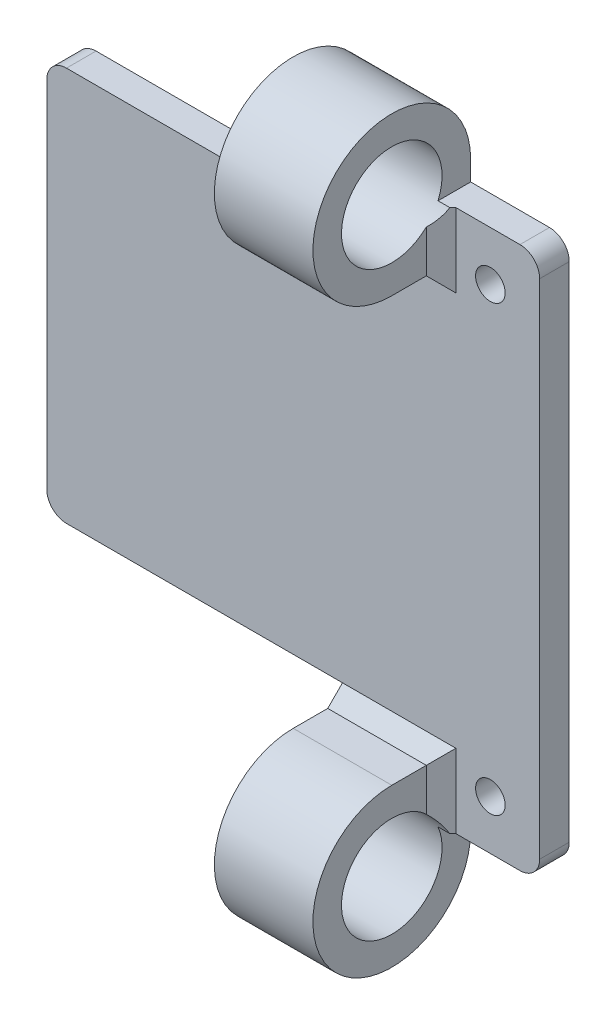
SolidWorks part; units mm, degrees
ref_plane "Front Plane" through (0, 0, 0) normal (0, 0, 1) x (1, 0, 0)
ref_plane "Top Plane" through (0, 0, 0) normal (0, 1, 0) x (1, 0, 0)
ref_plane "Right Plane" through (0, 0, 0) normal (1, 0, 0) x (0, 0, -1)
sketch "Sketch1" plane through (0, 0, 0) normal (0, 0, 1) x (1, 0, 0)
  line L0 (0, 0) -> (25, 0) construction
  line L1 (10, -27.5) -> (25, -27.5)
  line L2 (-25, -20) -> (-25, 20)
  line L3 (-5, 27.5) -> (25, 27.5)
  line L4 (25, -27.5) -> (25, 27.5)
  line L5 (25, 25.5) -> (25, -25.5) construction
  line L7 (20, 22.5) -> (20, -22.5) construction
  line L8 (-5, 27.5) -> (-5, 20)
  line L9 (-5, 20) -> (-25, 20)
  line L10 (-25, -20) -> (10, -20)
  line L11 (10, -20) -> (10, -27.5)
  line L12 (0, 0) -> (-25, 0) construction
  circle A0 centre (0, 22.5) radius 1.5
  circle A1 centre (20, 22.5) radius 1.5
  circle A2 centre (20, -22.5) radius 1.5
  point P0 (0, 0)
  point P14 (20, 0)
  point P21 (-25, 0)
  dimension "D3" = 3
  dimension "D1" = 50
  dimension "D2" = 55
  dimension "D4" = 30
  dimension "D5" = 20
  dimension "D6" = 5
  dimension "D7" = 45
  dimension "D8" = 40
  dimension "D9" = 15
extrude "Boss-Extrude1" add sketch "Sketch1" along normal blind 3
fillet "Fillet1" radius 2 4 edges at (25, 27.5, 1.5) (25, -27.5, 1.5) (-25, -20, 1.5) (-25, 20, 1.5)
sketch "Sketch2" plane through (0, 0, 0) normal (1, 0, 0) x (0, 0, -1)
  line L0 (0, 0) -> (-17.7596, 0) construction
  line L1 (-3, -25.5) -> (-3, 25.5) construction
  line L2 (-8, 21.5) -> (-3, 21.5)
  line L3 (0, -25.5) -> (0, 25.5) construction
  line L10 (0, 11.5) -> (-3, 11.5)
  line L11 (-3, 11.5) -> (-3, 21.5)
  line L12 (0, 11.5) -> (0, 29.5)
  line L13 (0, -11.5) -> (0, -29.5)
  line L14 (-3, -11.5) -> (-3, -21.5)
  line L15 (0, -11.5) -> (-3, -11.5)
  line L16 (-8, -21.5) -> (-3, -21.5)
  circle A0 centre (-8, 29.5) radius 5.1
  arc A1 (0, 29.5) -> (-8, 21.5) centre (-8, 29.5) ccw
  arc A5 (0, -29.5) -> (-8, -21.5) centre (-8, -29.5) cw
  circle A8 centre (-8, -29.5) radius 5.1
  dimension "D1" = 10.2
  dimension "D2" = 8
  dimension "D3" = 29.5
  dimension "D4" = 5
  dimension "D7" = 10
extrude "Boss-Extrude2" add sketch "Sketch2" along normal blind 10 from offset 5 contours A5 L13 L15 L14 L16 A8 | L12 A1 L2 L11 L10 A0 region at (0, 34.941, 13.441) region at (0, -20.5, 0.3053)
chamfer "Chamfer1" distance 2 angle 45 2 edges at (-5, 20, 1.5) (-5, 27.5, 1.5)
chamfer "Chamfer2" distance 1.5 angle 45 5 edges at (15, -24.5, 3) (10, -21.5, 3) (15, 24.5, 3) (5, 24.5, 3) (10, 21.5, 3)
